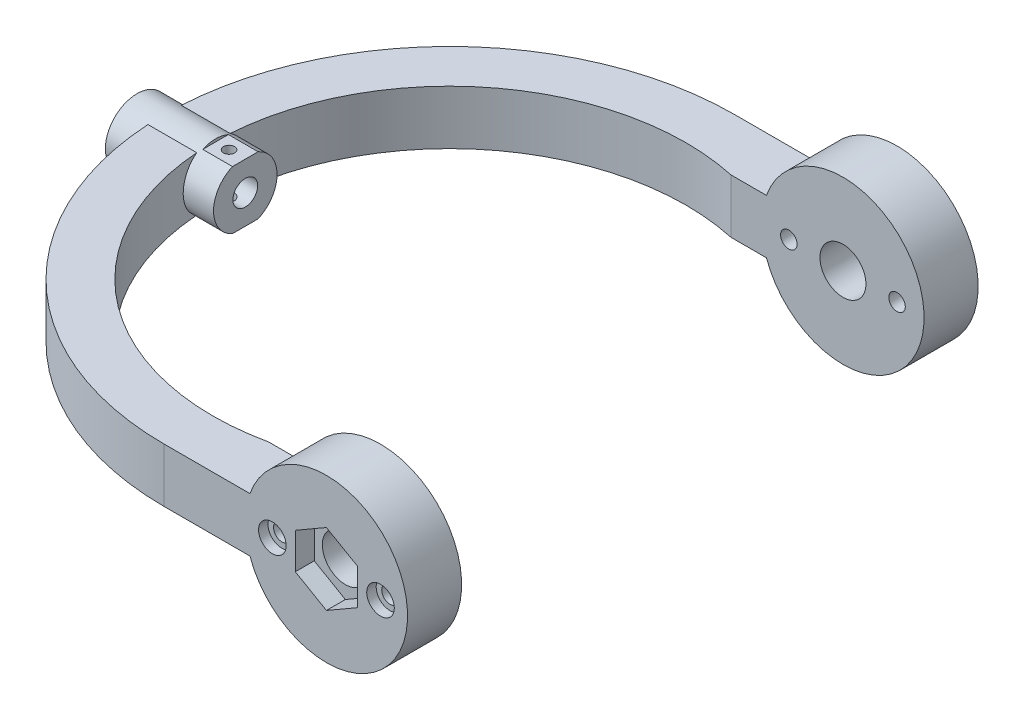
SolidWorks part; units mm, degrees
material "PLA"
ref_plane "Front Plane" through (0, 0, 0) normal (0, 0, 1) x (1, 0, 0)
ref_plane "Top Plane" through (0, 0, 0) normal (0, 1, 0) x (1, 0, 0)
ref_plane "Right Plane" through (0, 0, 0) normal (1, 0, 0) x (0, 0, -1)
sketch "Sketch1" plane through (0, 0, 0) normal (0, 1, 0) x (1, 0, 0)
  line L0 (0, -85.5) -> (0, 85.5) construction
  line L1 (0, 85.5) -> (80, 85.5)
  line L2 (0, -85.5) -> (80, -85.5)
  line L3 (80, 85.5) -> (80, -85.5) construction
  line L4 (80, 85.5) -> (80, 105.5)
  line L5 (80, -85.5) -> (80, -105.5)
  line L6 (80, -105.5) -> (0, -105.5)
  line L7 (80, 105.5) -> (0, 105.5)
  line L8 (0, -105.5) -> (0, 105.5) construction
  arc A0 (0, -85.5) -> (0, 85.5) centre (0, 0) cw
  arc A1 (0, 105.5) -> (0, -105.5) centre (0, 0) ccw
  dimension "D1" = 171
  dimension "D2" = 80
  dimension "D3" = 20
  dimension "D4" = 20
  dimension "D5" = 80
extrude "Boss-Extrude1" add sketch "Sketch1" along normal blind 10 and the other way blind 10 contours L7 A1 L6 L5 L2 A0 L1 L4 region at (-88.3095, 0, 0)
sketch "Sketch2" plane through (0, 0, 105.5) normal (0, 0, 1) x (1, 0, 0)
  line L0 (80, 10) -> (40, -10) construction
  line L1 (40, -10) -> (40, 10) construction
  line L2 (40, 10) -> (80, -10) construction
  line L3 (80, -10) -> (80, 10) construction
  line L4 (80, 10) -> (0, 10) construction
  line L5 (80, -10) -> (0, -10) construction
  circle A0 centre (60, 0) radius 30
  dimension "D1" = 60
  dimension "D2" = 40
extrude "Boss-Extrude2" add sketch "Sketch2" against normal blind 20
sketch "Sketch3" plane through (0, 0, 105.5) normal (0, 0, 1) x (1, 0, 0)
  line L0 (0, 0) -> (90, 0) construction
  circle A0 centre (60, 0) radius 8.5
  circle A1 centre (80, 0) radius 3.05
  circle A2 centre (40, 0) radius 3.05
  arc A3 (31.7157, -10) -> (31.7157, 10) centre (60, 0) ccw construction
  dimension "D1" = 17
  dimension "D2" = 6.1
  dimension "D3" = 6.1
  dimension "D4" = 20
  dimension "D5" = 20
extrude "Cut-Extrude1" cut sketch "Sketch3" against normal up to next
mirror "Mirror2" about plane through (0, 0, 0) normal (0, 0, 1) of "Boss-Extrude2", "Cut-Extrude1"
ref_axis "Axis1" through (60, 0, -130.2636) along (0, 0, 1)
sketch "Sketch6" plane through (0, 10, 0) normal (0, 1, 0) x (1, 0, 0)
  line L0 (31.7157, 85.5) -> (31.7157, 105.5) construction
  line L1 (31.7157, -85.5) -> (31.7157, -105.5) construction
  line L2 (31.7157, 81.5498) -> (31.7157, -81.5498)
  arc A0 (31.7157, 81.5498) -> (31.7157, -81.5498) centre (0, 0) ccw
  dimension "D1" = 87.5
extrude "Cut-Extrude3" cut sketch "Sketch6" against normal through all
sketch "Sketch7" plane through (0, 0, 105.5) normal (0, 0, 1) x (1, 0, 0)
  line L0 (60, -13.2791) -> (60, 13.2791) construction
  line L1 (60, 13.2791) -> (48.5, 6.6395)
  line L2 (48.5, 6.6395) -> (48.5, -6.6395)
  line L3 (48.5, -6.6395) -> (60, -13.2791)
  line L4 (60, -13.2791) -> (71.5, -6.6395)
  line L5 (71.5, -6.6395) -> (71.5, 6.6395)
  line L6 (71.5, 6.6395) -> (60, 13.2791)
  circle A1 centre (60, 0) radius 8.5
  circle A2 centre (60, 0) radius 11.5 construction
  dimension "D1" = 23
  dimension "D2" = 17
extrude "Cut-Extrude4" cut sketch "Sketch7" against normal blind 7
mirror "Mirror3" about plane through (0, 0, 0) normal (0, 0, 1) of "Cut-Extrude4"
ref_plane "Plane1" through (-105.5, 0, 0) normal (-1, 0, 0) x (0, 0, 1)
sketch "Sketch8" plane through (-105.5, 0, 0) normal (-1, 0, 0) x (0, 0, 1)
  circle A0 centre (0, 0) radius 11.75
  dimension "D1" = 23.5
extrude "Boss-Extrude3" add sketch "Sketch8" along normal blind 10 and the other way blind 20
sketch "Sketch9" plane through (-115.5, 0, 0) normal (-1, 0, 0) x (0, 0, 1)
  circle A0 centre (0, 0) radius 8.75
  dimension "D1" = 17.5
extrude "Cut-Extrude5" cut sketch "Sketch9" against normal blind 8
sketch "Sketch10" plane through (-107.5, 0, 0) normal (-1, 0, 0) x (0, 0, 1)
  circle A0 centre (0, 0) radius 4.57
  dimension "D1" = 9.14
extrude "Cut-Extrude6" cut sketch "Sketch10" against normal through all
ref_axis "Axis2" through (82.7145, 0, 0) along (-1, 0, 0)
sketch "Sketch11" plane through (-85.5, 0, 0) normal (1, 0, 0) x (0, 0, -1)
  circle A0 centre (0, 0) radius 11.75
  circle A1 centre (0, 0) radius 4.57
  dimension "D1" = 23.5
  dimension "D2" = 9.14
extrude "Boss-Extrude4" add sketch "Sketch11" along normal blind 10
sketch "Sketch12" plane through (0, 0, 0) normal (0, 1, 0) x (1, 0, 0)
  line L0 (-75.5, 0) -> (-81.5, 0) construction
  line L1 (-75.5, -11.75) -> (-75.5, 11.75) construction
  circle A0 centre (-81.5, 0) radius 2.05
  dimension "D2" = 4.1
  dimension "D1" = 6
extrude "Cut-Extrude7" cut sketch "Sketch12" against normal through all and the other way through all
sketch "Sketch13" plane through (0, 0, 105.5) normal (0, 0, 1) x (1, 0, 0)
  circle A0 centre (40, 0) radius 5.1
  circle A1 centre (40, 0) radius 3.05
  circle A2 centre (80, 0) radius 3.05
  circle A3 centre (80, 0) radius 5.1
  dimension "D1" = 10.2
  dimension "D2" = 10.2
  dimension "D3" = 6.1
  dimension "D4" = 6.1
extrude "Cut-Extrude8" cut sketch "Sketch13" against normal blind 3.5
mirror "Mirror4" about plane through (0, 0, 0) normal (0, 0, 1) of "Cut-Extrude8"
ref_plane "Plane2" through (0, 11.75, 0) normal (0, 1, 0) x (1, 0, 0)
sketch "Sketch14" plane through (0, 11.75, 0) normal (0, 1, 0) x (1, 0, 0)
  line L1 (-86.5, -11.75) -> (-75.5, -11.75)
  line L2 (-86.5, -11.75) -> (-86.5, 11.75)
  line L3 (-86.5, 11.75) -> (-75.5, 11.75)
  line L4 (-75.5, -11.75) -> (-75.5, 11.75)
  point P0 (-81.5, 0)
  dimension "D1" = 11
  dimension "D2" = 23.5
extrude "Cut-Extrude9" cut sketch "Sketch14" against normal blind 1
mirror "Mirror5" about plane through (0, 0, 0) normal (0, 1, 0) of "Cut-Extrude9"
